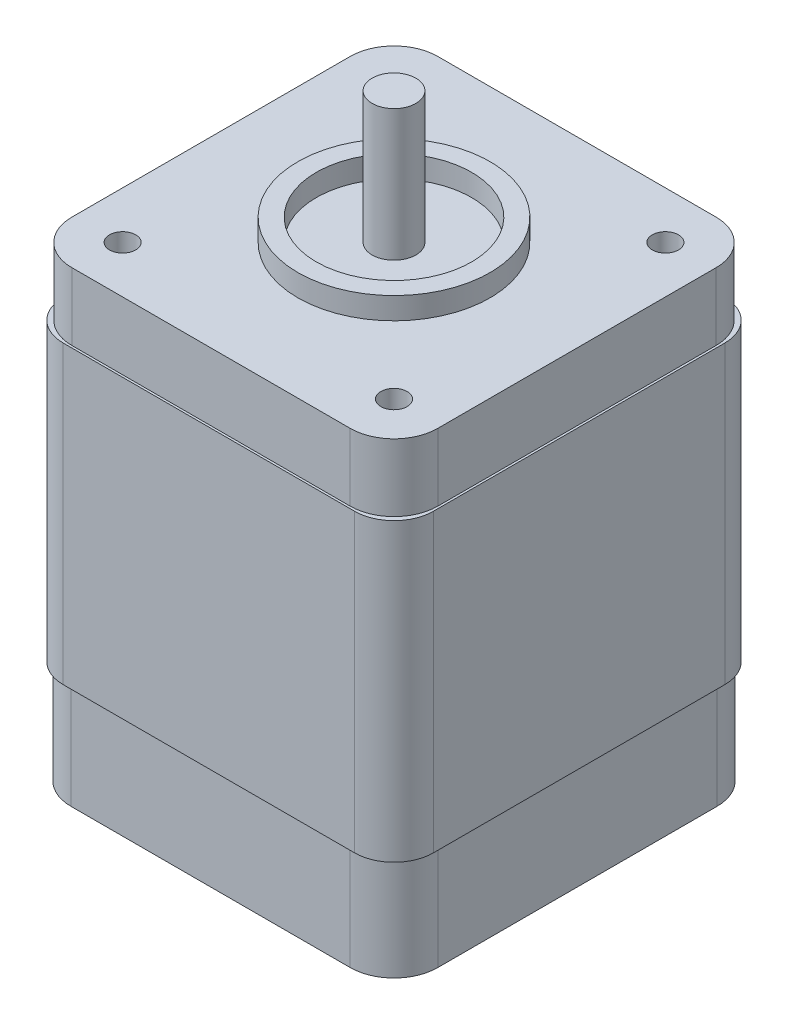
SolidWorks part; units mm, degrees
ref_plane "Front Plane" through (0, 0, 0) normal (0, 0, 1) x (1, 0, 0)
ref_plane "Top Plane" through (0, 0, 0) normal (0, 1, 0) x (1, 0, 0)
ref_plane "Right Plane" through (0, 0, 0) normal (1, 0, 0) x (0, 0, -1)
sketch "Sketch1" plane through (0, 0, 0) normal (0, 1, 0) x (1, 0, 0)
  line L1 (20.95, -20.95) -> (-20.95, -20.95)
  line L2 (20.95, -20.95) -> (20.95, 20.95)
  line L3 (20.95, 20.95) -> (-20.95, 20.95)
  line L4 (-20.95, -20.95) -> (-20.95, 20.95)
  line L5 (20.95, -20.95) -> (-20.95, 20.95) construction
  line L6 (20.95, 20.95) -> (-20.95, -20.95) construction
  point P0 (0, 0)
  dimension "D1" = 41.9
extrude "Boss-Extrude1" add sketch "Sketch1" along normal blind 11.8
sketch "Sketch2" plane through (0, 11.8, 0) normal (0, 1, 0) x (1, 0, 0)
  line L1 (21.15, -21.15) -> (-21.15, -21.15)
  line L2 (21.15, -21.15) -> (21.15, 21.15)
  line L3 (21.15, 21.15) -> (-21.15, 21.15)
  line L4 (-21.15, -21.15) -> (-21.15, 21.15)
  line L5 (21.15, -21.15) -> (-21.15, 21.15) construction
  line L6 (21.15, 21.15) -> (-21.15, -21.15) construction
  point P0 (0, 0)
  dimension "D1" = 42.3
extrude "Boss-Extrude2" add sketch "Sketch2" along normal blind 33.8
sketch "Sketch3" plane through (0, 45.6, 0) normal (0, 1, 0) x (1, 0, 0)
  line L1 (20.9, -20.9) -> (-20.9, -20.9)
  line L2 (20.9, -20.9) -> (20.9, 20.9)
  line L3 (20.9, 20.9) -> (-20.9, 20.9)
  line L4 (-20.9, -20.9) -> (-20.9, 20.9)
  line L5 (20.9, -20.9) -> (-20.9, 20.9) construction
  line L6 (20.9, 20.9) -> (-20.9, -20.9) construction
  point P0 (0, 0)
  dimension "D1" = 41.8
extrude "Boss-Extrude3" add sketch "Sketch3" along normal blind 7.7
sketch "Sketch4" plane through (0, 53.3, 0) normal (0, 1, 0) x (1, 0, 0)
  circle A0 centre (0, 0) radius 10.98
  circle A1 centre (0, 0) radius 8.875
  dimension "D1" = 21.96
  dimension "D2" = 17.75
extrude "Boss-Extrude4" add sketch "Sketch4" along normal blind 2.5
fillet "Fillet1" radius 5 8 edges at (-20.95, 5.9, -20.95) (20.9, 49.45, -20.9) (20.95, 5.9, -20.95) (20.95, 5.9, 20.95) (-20.9, 49.45, 20.9) (-20.95, 5.9, 20.95) (-20.9, 49.45, -20.9) (20.9, 49.45, 20.9)
fillet "Fillet3" radius 4.5 4 edges at (-21.15, 28.7, 21.15) (21.15, 28.7, 21.15) (21.15, 28.7, -21.15) (-21.15, 28.7, -21.15)
sketch "Sketch5" plane through (0, 53.3, 0) normal (0, 1, 0) x (1, 0, 0)
  circle A0 centre (0, 0) radius 2.5
  dimension "D1" = 5
extrude "Boss-Extrude5" add sketch "Sketch5" along normal blind 15
sketch "Sketch6" plane through (0, 53.3, 0) normal (0, 1, 0) x (1, 0, 0)
  line L1 (15.5, 15.5) -> (-15.5, 15.5) construction
  line L2 (15.5, 15.5) -> (15.5, -15.5) construction
  line L3 (15.5, -15.5) -> (-15.5, -15.5) construction
  line L4 (-15.5, 15.5) -> (-15.5, -15.5) construction
  line L5 (15.5, 15.5) -> (-15.5, -15.5) construction
  line L6 (15.5, -15.5) -> (-15.5, 15.5) construction
  circle A0 centre (-15.5, -15.5) radius 1.5
  circle A1 centre (-15.5, 15.5) radius 1.5
  circle A2 centre (15.5, 15.5) radius 1.5
  circle A3 centre (15.5, -15.5) radius 1.5
  point P0 (0, 0)
  dimension "D1" = 3
  dimension "D2" = 31
extrude "Cut-Extrude1" cut sketch "Sketch6" against normal blind 5
sketch "Sketch7" plane through (0, 0, 0) normal (0, -1, 0) x (1, 0, 0)
  line L0 (-20.95, -15.95) -> (-20.95, 15.95) construction
  line L1 (-20.95, 13.5) -> (-23.15, 13.5)
  line L2 (-20.95, 13.5) -> (-20.95, -13.5)
  line L3 (-20.95, -13.5) -> (-23.15, -13.5)
  line L4 (-23.15, 13.5) -> (-23.15, -13.5)
  point P6 (-23.15, 0)
  dimension "D1" = 27
  dimension "D2" = 2.2
extrude "Boss-Extrude6" add sketch "Sketch7" against normal blind 11.8
fillet "Fillet5" radius 3 2 edges at (-20.95, 5.9, 13.5) (-20.95, 5.9, -13.5)
